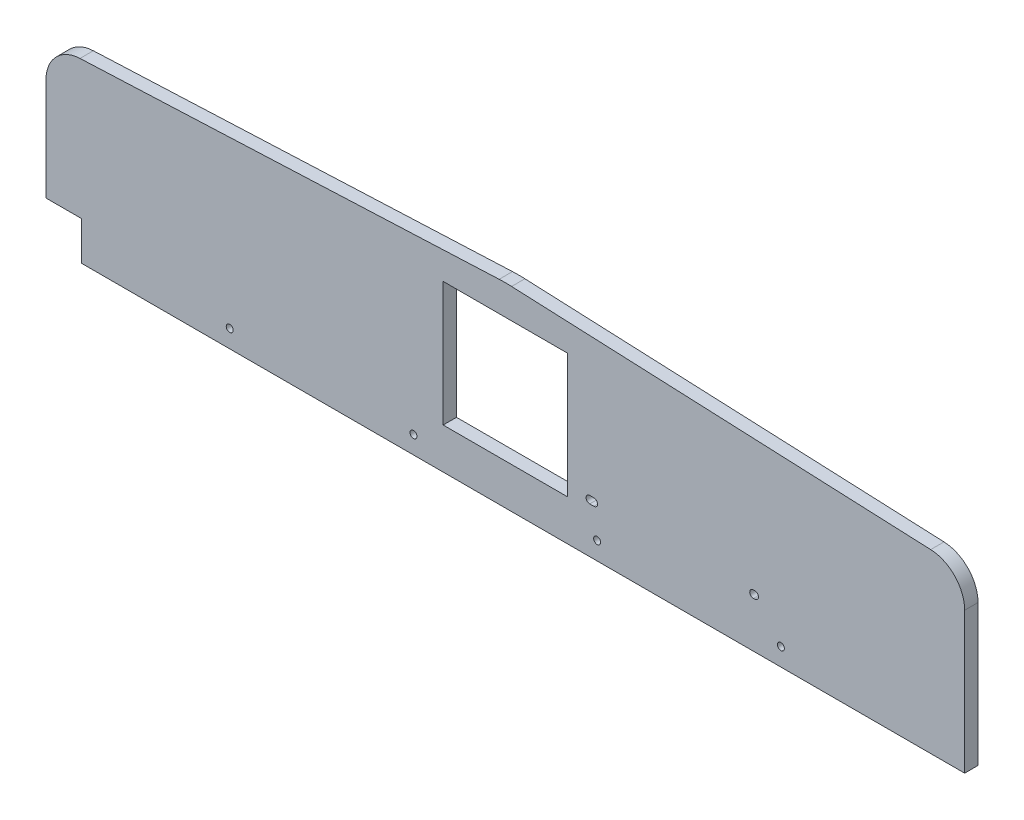
SolidWorks part; units mm, degrees
material "PC High Viscosity"
ref_plane "Front Plane" through (0, 0, 0) normal (0, 0, 1) x (1, 0, 0)
ref_plane "Top Plane" through (0, 0, 0) normal (0, 1, 0) x (1, 0, 0)
ref_plane "Right Plane" through (0, 0, 0) normal (1, 0, 0) x (0, 0, -1)
sketch "Sketch2" plane through (0, 0, 0) normal (0, 0, 1) x (1, 0, 0)
  line L0 (-328.3315, 55.6895) -> (-328.3315, 154.4895)
  line L1 (-328.3315, 154.4895) -> (0, 168.8465)
  line L2 (0, 168.8465) -> (328.2858, 154.4895)
  line L3 (328.2858, 154.4895) -> (328.2858, 55.6895)
  line L4 (328.2858, 55.6895) -> (328.2858, 29.2895)
  line L6 (328.2858, 29.2895) -> (-328.3315, 29.2895)
  line L7 (-328.3315, 29.2895) -> (-328.3315, 55.6895)
  dimension "D1" = 113.157
  dimension "D7" = 328.2858
  dimension "D8" = 98.8
  dimension "D9" = 26.4
extrude "Boss-Extrude1" add sketch "Sketch2" along normal mid plane 9.525
fillet "Fillet1" radius 25.4 2 edges at (328.2858, 154.4895, 0) (-328.3315, 154.4895, 0)
fillet "Fillet2" radius 101.6 1 edges at (0, 168.8465, 0)
sketch "Sketch3" plane through (0, 0, 4.7625) normal (0, 0, 1) x (1, 0, 0)
  line L0 (0, 0) -> (0, 192.0016) construction
  line L1 (-328.3315, 29.2895) -> (-302.9315, 29.2895)
  line L2 (-328.3315, 29.2895) -> (-328.3315, 56.9755)
  line L3 (-328.3315, 56.9755) -> (-302.9315, 56.9755)
  line L4 (-302.9315, 29.2895) -> (-302.9315, 56.9755)
  line L5 (0, 192.0016) -> (0, -60.0751) construction
  dimension "D1" = 25.4
  dimension "D2" = 27.686
extrude "Cut-Extrude1" cut sketch "Sketch3" against normal through all
sketch "Sketch5" plane through (0, 0, 4.7625) normal (0, 0, 1) x (1, 0, 0)
  line L1 (-44.45, 147.336) -> (44.45, 147.336)
  line L2 (-44.45, 147.336) -> (-44.45, 58.436)
  line L3 (-44.45, 58.436) -> (44.45, 58.436)
  line L4 (44.45, 147.336) -> (44.45, 58.436)
  line L5 (-44.45, 147.336) -> (44.45, 58.436) construction
  line L6 (-44.45, 58.436) -> (44.45, 147.336) construction
  point P0 (0, 102.886)
  dimension "D1" = 88.9
  dimension "D2" = 88.9
extrude "Cut-Extrude2" cut sketch "Sketch5" against normal through all
hole_wizard "Tap Drill for M6x1.0 Tap1" positions "Sketch7" profile "Sketch6" hole size "M6x1.0" standard "ANSI Metric" end condition through all
sketch "Sketch7" plane through (0, 0, 4.7625) normal (0, 0, 1) x (1, 0, 0)
  line L0 (-302.9315, 29.2895) -> (328.2858, 29.2895) construction
  line L1 (-328.3315, 130.1759) -> (-328.3315, 56.9755) construction
  point P0 (-197.0135, 41.9895)
  point P2 (-65.6955, 41.9895)
  point P4 (65.6225, 41.9895)
  point P6 (196.9405, 41.9895)
  dimension "D1" = 12.7
  dimension "D2" = 131.318
  dimension "D3" = 131.318
  dimension "D4" = 131.318
  dimension "D5" = 131.318
sketch "Sketch6" plane through (-197.0135, 41.9895, 4.7625) normal (1, 0, 0) x (0, -1, 0)
  line L0 (0, 0) -> (0, 9.525)
  line L1 (0, 9.525) -> (2.5, 9.525)
  line L2 (2.5, 9.525) -> (2.5, 0)
  line L5 (2.5, 0) -> (0, 0)
  line L11 (0, -6.35) -> (0, 107.95) construction
  dimension "Thru Hole Dia." = 5
  dimension "Thru Hole Depth" = 9.525
sketch "Sketch8" plane through (0, 0, 4.7625) normal (0, 0, 1) x (1, 0, 0)
  line L0 (177.2858, 64.5895) -> (178.2858, 64.5895) construction
  line L1 (177.2858, 67.2145) -> (178.2858, 67.2145)
  line L2 (177.2858, 61.9645) -> (178.2858, 61.9645)
  line L3 (63.2858, 64.5895) -> (60.2858, 64.5895) construction
  line L4 (63.2858, 61.9645) -> (60.2858, 61.9645)
  line L5 (63.2858, 67.2145) -> (60.2858, 67.2145)
  line L6 (-302.9315, 29.2895) -> (328.2858, 29.2895) construction
  line L7 (328.2858, 29.2895) -> (328.2858, 130.176) construction
  arc A0 (177.2858, 67.2145) -> (177.2858, 61.9645) centre (177.2858, 64.5895) ccw
  arc A1 (178.2858, 61.9645) -> (178.2858, 67.2145) centre (178.2858, 64.5895) ccw
  arc A2 (63.2858, 61.9645) -> (63.2858, 67.2145) centre (63.2858, 64.5895) ccw
  arc A3 (60.2858, 67.2145) -> (60.2858, 61.9645) centre (60.2858, 64.5895) ccw
  point P2 (177.7858, 64.5895)
  point P9 (61.7858, 64.5895)
  point P20 (228.7858, 64.5895)
  dimension "D2" = 1
  dimension "D1" = 2.625
  dimension "D3" = 35.3
  dimension "D4" = 150
  dimension "D5" = 114
  dimension "D6" = 3
extrude "Cut-Extrude3" cut sketch "Sketch8" against normal through all
